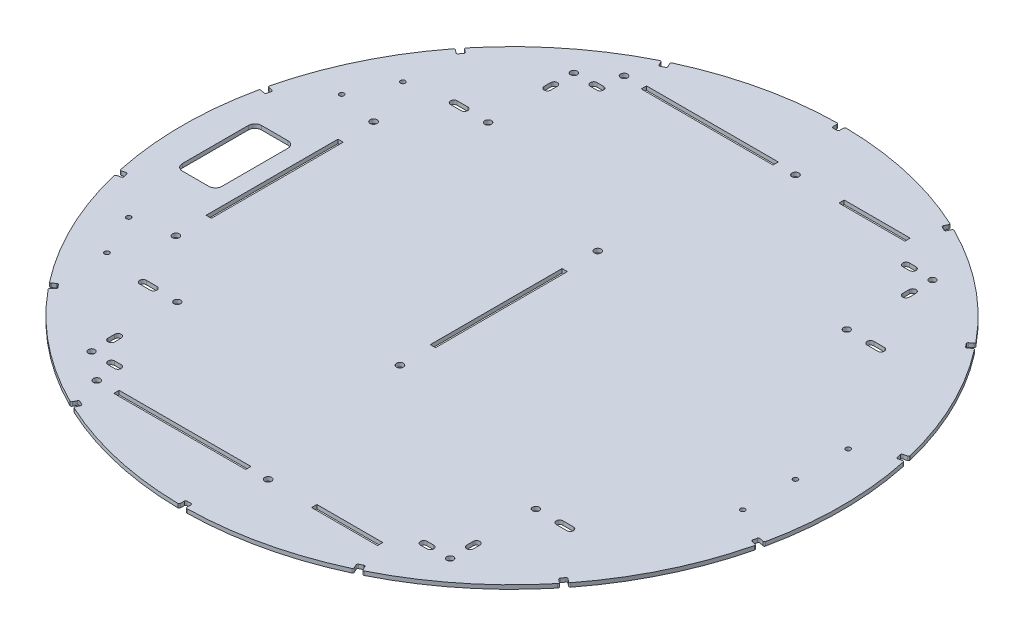
SolidWorks part; units mm, degrees
ref_plane "Front Plane" through (0, 0, 0) normal (0, 0, 1) x (1, 0, 0)
ref_plane "Top Plane" through (0, 0, 0) normal (0, 1, 0) x (1, 0, 0)
ref_plane "Right Plane" through (0, 0, 0) normal (1, 0, 0) x (0, 0, -1)
sketch "Sketch1" plane through (0, 0, 0) normal (0, 1, 0) x (1, 0, 0)
  circle A0 centre (0, 0) radius 250
extrude "Boss-Extrude1" add sketch "Sketch1" along normal blind 3
sketch "Sketch11" plane through (0, 3, 0) normal (0, 1, 0) x (1, 0, 0)
  line L1 (1.5, 245) -> (-1.5, 245)
  line L2 (2.5, 246) -> (2.5, 255)
  line L3 (2.5, 255) -> (-2.5, 255)
  line L4 (-2.5, 246) -> (-2.5, 255)
  line L5 (2.5, 245) -> (-2.5, 255) construction
  line L6 (2.5, 255) -> (-2.5, 245) construction
  circle A0 centre (0, 0) radius 250 construction
  arc A1 (2.5, 246) -> (1.5, 245) centre (1.5, 246) cw
  arc A2 (-1.5, 245) -> (-2.5, 246) centre (-1.5, 246) cw
  point P0 (0, 250)
  dimension "D3" = 1
  dimension "D1" = 10
  dimension "D2" = 5
extrude "Cut-Extrude5" cut sketch "Sketch11" against normal blind 4
fillet "Fillet1" radius 1 2 edges at (2.5, 1.5, -249.9875) (-2.5, 1.5, -249.9875)
pattern_circular "CirPattern1" count 14 over 360 about axis through (0, 3, 0) along (0, -1, 0) of "Cut-Extrude5", "Fillet1"
sketch "Sketch17" plane through (0, 3, 0) normal (0, 1, 0) x (1, 0, 0)
  line L0 (-8, -50) -> (-8, 50)
  line L1 (-182, -50) -> (-178, -50)
  line L2 (-182, -50) -> (-182, 50)
  line L3 (-182, 50) -> (-178, 50)
  line L4 (-178, -50) -> (-178, 50)
  line L5 (-182, -50) -> (-178, 50) construction
  line L6 (-182, 50) -> (-178, -50) construction
  line L7 (-12, 50) -> (-8, 50)
  line L8 (-12, -50) -> (-12, 50)
  line L9 (-12, -50) -> (-8, -50)
  point P0 (-180, 0)
  dimension "D1" = 100
  dimension "D2" = 4
  dimension "D3" = 0
  dimension "D4" = 180
  dimension "D5" = 2
extrude "Cut-Extrude11" cut sketch "Sketch17" against normal blind 10
sketch "Sketch18" plane through (0, 3, 0) normal (0, 1, 0) x (1, 0, 0)
  line L0 (-178, -50) -> (-178, 50) construction
  line L1 (-1.65, 0) -> (1.65, 0) construction
  circle A0 centre (-180, 75) radius 2.6
  circle A1 centre (-180, -75) radius 2.6
  circle A2 centre (-10, 75) radius 2.6
  circle A3 centre (-10, -75) radius 2.6
  point P4 (-178, 0)
  dimension "D1" = 75
  dimension "D2" = 2
extrude "Cut-Extrude12" cut sketch "Sketch18" against normal blind 10
sketch "Sketch20" plane through (0, 0, 0) normal (0, -1, 0) x (1, 0, 0)
  line L0 (-166.5, -117.9) -> (-148.647, -117.9) construction
  line L1 (-162, -117.9) -> (-154, -117.9) construction
  line L2 (-162, -115.4) -> (-154, -115.4)
  line L3 (-162, -120.4) -> (-154, -120.4)
  line L4 (0, -1.65) -> (0, 1.65) construction
  line L5 (166.5, -117.9) -> (148.647, -117.9) construction
  line L6 (162, -117.9) -> (154, -117.9) construction
  line L7 (162, -115.4) -> (154, -115.4)
  line L8 (162, -120.4) -> (154, -120.4)
  line L9 (1.65, 0) -> (-1.65, 0) construction
  line L10 (162, 117.9) -> (154, 117.9) construction
  line L11 (162, 115.4) -> (154, 115.4)
  line L12 (162, 120.4) -> (154, 120.4)
  line L13 (-162, 117.9) -> (-154, 117.9) construction
  line L14 (-162, 115.4) -> (-154, 115.4)
  line L15 (-162, 120.4) -> (-154, 120.4)
  line L16 (-166.5, 117.9) -> (-148.647, 117.9) construction
  line L17 (166.5, 117.9) -> (148.647, 117.9) construction
  arc A0 (-164, -115.4) -> (-164, -120.4) centre (-164, -117.9) ccw construction
  arc A1 (-162, -115.4) -> (-162, -120.4) centre (-162, -117.9) ccw
  arc A2 (-154, -120.4) -> (-154, -115.4) centre (-154, -117.9) ccw
  arc A3 (162, -115.4) -> (162, -120.4) centre (162, -117.9) cw
  arc A4 (154, -120.4) -> (154, -115.4) centre (154, -117.9) cw
  arc A5 (162, 115.4) -> (162, 120.4) centre (162, 117.9) ccw
  arc A6 (154, 120.4) -> (154, 115.4) centre (154, 117.9) ccw
  arc A7 (-162, 115.4) -> (-162, 120.4) centre (-162, 117.9) cw
  arc A8 (-154, 120.4) -> (-154, 115.4) centre (-154, 117.9) cw
  point P8 (-158, -117.9)
  point P20 (158, -117.9)
  point P29 (158, 117.9)
  point P36 (-158, 117.9)
  dimension "D1" = 2.5
  dimension "D2" = 8
  dimension "D3" = 158
extrude "Cut-Extrude14" cut sketch "Sketch20" against normal blind 14
sketch "Sketch21" plane through (0, 3, 0) normal (0, 1, 0) x (1, 0, 0)
  line L0 (-1.65, 0) -> (1.65, 0) construction
  line L1 (0, 198) -> (-100, 198)
  line L2 (0, 198) -> (0, 202)
  line L3 (0, 202) -> (-100, 202)
  line L4 (-100, 198) -> (-100, 202)
  line L5 (0, 198) -> (-100, 202) construction
  line L6 (0, 202) -> (-100, 198) construction
  line L7 (0, -202) -> (-100, -198) construction
  line L8 (0, -198) -> (-100, -202) construction
  line L9 (-100, -198) -> (-100, -202)
  line L10 (0, -202) -> (-100, -202)
  line L11 (0, -198) -> (0, -202)
  line L12 (0, -198) -> (-100, -198)
  circle A0 centre (-115, 200) radius 2.6
  circle A1 centre (15, 200) radius 2.6
  circle A2 centre (15, -200) radius 2.6
  circle A3 centre (-115, -200) radius 2.6
  point P0 (-50, 200)
  point P13 (-50, -200)
  dimension "D5" = 65
  dimension "D6" = 65
  dimension "D1" = 4
  dimension "D2" = 100
  dimension "D3" = 200
  dimension "D4" = 50
extrude "Cut-Extrude15" cut sketch "Sketch21" against normal blind 14
sketch "Sketch22" plane through (0, 3, 0) normal (0, 1, 0) x (1, 0, 0)
  line L0 (-1.65, 0) -> (1.65, 0) construction
  line L1 (0, -1.65) -> (0, 1.65) construction
  circle A0 centre (-136, -117.9) radius 2.5
  circle A1 centre (-136, 117.9) radius 2.5
  circle A2 centre (136, 117.9) radius 2.5
  circle A3 centre (136, -117.9) radius 2.5
  circle A4 centre (-136, 182.9) radius 2.5
  circle A5 centre (136, 182.9) radius 2.5
  circle A6 centre (-136, -182.9) radius 2.5
  circle A7 centre (136, -182.9) radius 2.5
  dimension "D1" = 2
extrude "Cut-Extrude16" cut sketch "Sketch22" against normal blind 14
sketch "Sketch24" plane through (0, 0, 0) normal (0, -1, 0) x (1, 0, 0)
  line L1 (-200, -30) -> (-220, -30)
  line L2 (-195, -25) -> (-195, 25)
  line L3 (-200, 30) -> (-220, 30)
  line L4 (-225, -25) -> (-225, 25)
  line L5 (-195, -30) -> (-225, 30) construction
  line L6 (-195, 30) -> (-225, -30) construction
  arc A0 (-195, -25) -> (-200, -30) centre (-200, -25) cw
  arc A1 (-220, -30) -> (-225, -25) centre (-220, -25) cw
  arc A2 (-195, 25) -> (-200, 30) centre (-200, 25) ccw
  arc A3 (-225, 25) -> (-220, 30) centre (-220, 25) cw
  point P0 (-210, 0)
  dimension "D1" = 5
extrude "Cut-Extrude17" cut sketch "Sketch24" against normal blind 14
sketch "Sketch25" plane through (0, 3, 0) normal (0, 1, 0) x (1, 0, 0)
  line L1 (50, 202) -> (100, 202)
  line L2 (50, 202) -> (50, 198)
  line L3 (50, 198) -> (100, 198)
  line L4 (100, 202) -> (100, 198)
  line L5 (50, -198) -> (100, -198)
  line L6 (50, -198) -> (50, -202)
  line L7 (50, -202) -> (100, -202)
  line L8 (100, -198) -> (100, -202)
extrude "Cut-Extrude18" cut sketch "Sketch25" against normal blind 4
sketch "Sketch26" plane through (0, 3, 0) normal (0, 1, 0) x (1, 0, 0)
  line L0 (-136, 162.9) -> (-136, 167.9) construction
  line L1 (-138.5, 162.9) -> (-138.5, 167.9)
  line L2 (-133.5, 162.9) -> (-133.5, 167.9)
  line L3 (-116, 182.9) -> (-121, 182.9) construction
  line L4 (-116, 180.4) -> (-121, 180.4)
  line L5 (-116, 185.4) -> (-121, 185.4)
  line L6 (0, -1.65) -> (0, 1.65) construction
  line L7 (116, 182.9) -> (121, 182.9) construction
  line L8 (116, 180.4) -> (121, 180.4)
  line L9 (116, 185.4) -> (121, 185.4)
  line L10 (136, 162.9) -> (136, 167.9) construction
  line L11 (138.5, 162.9) -> (138.5, 167.9)
  line L12 (133.5, 162.9) -> (133.5, 167.9)
  line L13 (-1.65, 0) -> (1.65, 0) construction
  line L14 (116, -182.9) -> (121, -182.9) construction
  line L15 (116, -180.4) -> (121, -180.4)
  line L16 (116, -185.4) -> (121, -185.4)
  line L17 (136, -162.9) -> (136, -167.9) construction
  line L18 (138.5, -162.9) -> (138.5, -167.9)
  line L19 (133.5, -162.9) -> (133.5, -167.9)
  line L20 (-136, -162.9) -> (-136, -167.9) construction
  line L21 (-138.5, -162.9) -> (-138.5, -167.9)
  line L22 (-133.5, -162.9) -> (-133.5, -167.9)
  line L23 (-116, -182.9) -> (-121, -182.9) construction
  line L24 (-116, -180.4) -> (-121, -180.4)
  line L25 (-116, -185.4) -> (-121, -185.4)
  arc A0 (-138.5, 162.9) -> (-133.5, 162.9) centre (-136, 162.9) ccw
  arc A1 (-133.5, 167.9) -> (-138.5, 167.9) centre (-136, 167.9) ccw
  circle A2 centre (-136, 182.9) radius 2.5 construction
  arc A3 (-116, 180.4) -> (-116, 185.4) centre (-116, 182.9) ccw
  arc A4 (-121, 185.4) -> (-121, 180.4) centre (-121, 182.9) ccw
  arc A5 (116, 180.4) -> (116, 185.4) centre (116, 182.9) cw
  arc A6 (121, 185.4) -> (121, 180.4) centre (121, 182.9) cw
  arc A7 (138.5, 162.9) -> (133.5, 162.9) centre (136, 162.9) cw
  arc A8 (133.5, 167.9) -> (138.5, 167.9) centre (136, 167.9) cw
  arc A9 (116, -180.4) -> (116, -185.4) centre (116, -182.9) ccw
  arc A10 (121, -185.4) -> (121, -180.4) centre (121, -182.9) ccw
  arc A11 (138.5, -162.9) -> (133.5, -162.9) centre (136, -162.9) ccw
  arc A12 (133.5, -167.9) -> (138.5, -167.9) centre (136, -167.9) ccw
  arc A13 (-138.5, -162.9) -> (-133.5, -162.9) centre (-136, -162.9) cw
  arc A14 (-133.5, -167.9) -> (-138.5, -167.9) centre (-136, -167.9) cw
  arc A15 (-116, -180.4) -> (-116, -185.4) centre (-116, -182.9) cw
  arc A16 (-121, -185.4) -> (-121, -180.4) centre (-121, -182.9) cw
  point P3 (-136, 165.4)
  point P12 (-118.5, 182.9)
  point P21 (118.5, 182.9)
  point P28 (136, 165.4)
  point P37 (118.5, -182.9)
  point P44 (136, -165.4)
  point P51 (-136, -165.4)
  point P58 (-118.5, -182.9)
  dimension "D1" = 2.5
  dimension "D4" = 2.5
  dimension "D2" = 5
  dimension "D3" = 17.5
  dimension "D5" = 5
  dimension "D6" = 17.5
extrude "Cut-Extrude19" cut sketch "Sketch26" against normal blind 4
sketch "Sketch27" plane through (0, 3, 0) normal (0, 1, 0) x (1, 0, 0)
  circle A0 centre (215, 0) radius 1.8
  circle A2 centre (215, 40) radius 1.8
  circle A3 centre (215, -40) radius 1.8
  dimension "D1" = 2
  dimension "D3" = 215
  dimension "D2" = 2
extrude "Cut-Extrude20" cut sketch "Sketch27" against normal blind 10
sketch "Sketch28" plane through (0, 3, 0) normal (0, 1, 0) x (1, 0, 0)
  line L0 (-200, 30) -> (-220, 30) construction
  line L1 (-1.65, 0) -> (1.65, 0) construction
  circle A0 centre (-210, 80.7775) radius 1.8
  circle A2 centre (0, 0) radius 225
  circle A3 centre (-195, 112.2497) radius 1.8
  circle A4 centre (-195, -112.2497) radius 1.8
  circle A5 centre (-210, -80.7775) radius 1.8
  point P6 (-210, 30)
  dimension "D1" = 15
  dimension "D2" = 0
  dimension "D3" = 450
extrude "Cut-Extrude21" cut sketch "Sketch28" against normal blind 10 contours A2 A3 | A2 A3 | A2 A0 | A0 A2 | A5 | A4 region at (-209.2858, 3, -80.5027) region at (-210.7118, 3, -81.0513) region at (-195.661, 3, -112.6302) region at (-194.3368, 3, -111.868)
